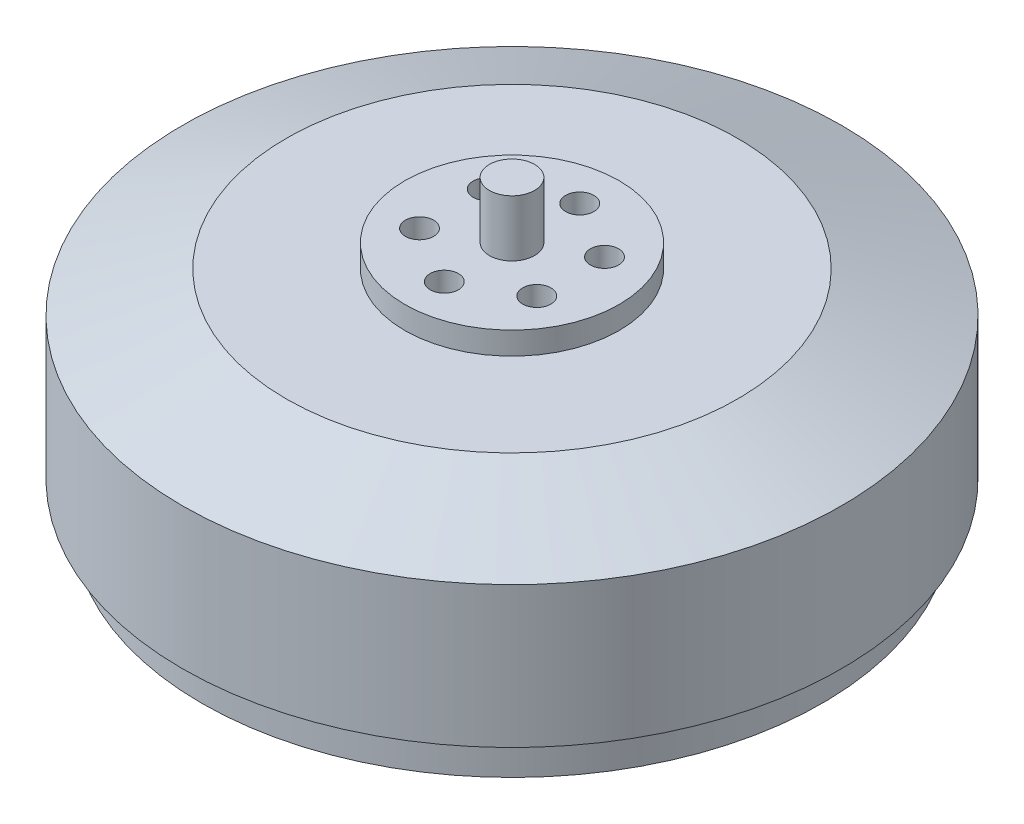
SolidWorks part; units mm, degrees
note: '?' marks a value the reader was unsure of.
ref_plane "Спереди" through (0, 0, 0) normal (0, 0, 1) x (1, 0, 0)
ref_plane "Сверху" through (0, 0, 0) normal (0, 1, 0) x (1, 0, 0)
ref_plane "Справа" through (0, 0, 0) normal (1, 0, 0) x (0, 0, -1)
ref_axis "Axis1" through (0, 5.1843, 0) along (0, 1, 0)?
sketch "Sketch1" plane through (0, 0, 0) normal (0, 0, 1) x (1, 0, 0)
  line L0 (0, 0) -> (0, -21846.0163) construction
  line L1 (0, 15.8) -> (0, -15.8)
  line L2 (0, 15.8) -> (-2, 15.8)
  line L3 (-2, 15.8) -> (-2, 10.8)
  line L4 (-2, 10.8) -> (-9.5, 10.8)
  line L5 (-9.5, 10.8) -> (-9.5, 8.8)
  line L6 (-9.5, 8.8) -> (-20, 8.8)
  line L7 (-20, 8.8) -> (-29.2, 5.2)
  line L8 (-29.2, 5.2) -> (-29.2, -7.3)
  line L9 (-29.2, -7.3) -> (-27.5, -7.3)
  line L10 (-27.5, -7.3) -> (-27.5, -10.8)
  line L11 (-27.5, -10.8) -> (-12.5, -10.8)
  line L12 (-12.5, -10.8) -> (-12.5, -15.8)
  line L13 (-12.5, -15.8) -> (0, -15.8)
  point P5 (0, 0)
  dimension "D1" = 58.4
  dimension "D2" = 4
  dimension "D3" = 19
  dimension "D4" = 40
  dimension "D5" = 5
  dimension "D6" = 2
  dimension "D7" = 3.6
  dimension "D8" = 12.5
  dimension "D9" = 3.5
  dimension "D10" = 5
  dimension "D11" = 55
  dimension "D12" = 25
revolve "Revolve1" add sketch "Sketch1" angle 360 about L0
sketch "Sketch2" plane through (0, -15.8, 0) normal (0, -1, 0) x (1, 0, 0)
  circle A0 centre (0, 12.5) radius 5
  circle A1 centre (0, 0) radius 12.5 construction
  circle A2 centre (12.5, 0) radius 5
  circle A3 centre (0, -12.5) radius 5
  circle A4 centre (-12.5, 0) radius 5
  point P14 (0, 0)
  dimension "D1" = 10
  dimension "D2" = 4
extrude "Boss-Extrude1" add sketch "Sketch2" against normal up to next
fillet "Fillet1" radius 2 8 edges at (11.5, -13.3, -4.899) (11.5, -13.3, 4.899) (-4.899, -13.3, -11.5) (4.899, -13.3, -11.5) (-11.5, -13.3, 4.899) (-11.5, -13.3, -4.899) (4.899, -13.3, 11.5) (-4.899, -13.3, 11.5)
hole_wizard "M3x0.5 Tapped Hole1" positions "Sketch3" profile "Sketch4" tap size "M3x0.5" standard "ANSI Metric"
sketch "Sketch3" plane through (0, -15.8, 0) normal (0, -1, 0) x (-1, 0, 0)
  point P0 (0, -12.5)
  point P3 (-12.5, 0)
  point P6 (0, 12.5)
  point P9 (12.5, 0)
sketch "Sketch4" plane through (0, -15.8, 12.5) normal (1, 0, 0) x (0, 0, -1)
  line L0 (0, 0) -> (0, 4.7511)
  line L1 (0, 4.7511) -> (1.25, 4)
  line L2 (1.25, 4) -> (1.25, 0)
  line L5 (1.25, 0) -> (0, 0)
  line L10 (0, 4.7511) -> (-1.25, 4) construction
  line L11 (0, -6.35) -> (0, 107.95) construction
  dimension "Tap Drill Dia." = 2.5
  dimension "Tap Drill Depth" = 4
  dimension "Drill Angle" = 118
cosmetic thread "Hole Thread1" parameters "D1"=4, "D2"=3
cosmetic thread "Hole Thread2" parameters "D1"=4, "D2"=3
cosmetic thread "Hole Thread3" parameters "D1"=4, "D2"=3
cosmetic thread "Hole Thread4" parameters "D1"=4, "D2"=3
sketch "Sketch5" plane through (0, 0, 0) normal (0, 0, 1) x (1, 0, 0)
  line L0 (0, 0) -> (0, -50000) construction
  line L1 (-4.998, -15.8) -> (4.998, -15.8) construction
  line L2 (0, -15.8) -> (-3.4, -15.8)
  line L3 (0, -15.8) -> (0, -19.3)
  line L4 (0, -19.3) -> (-3.4, -19.3)
  line L6 (-3.4, -15.8) -> (-3.4, -17.3)
  line L7 (-3.4, -17.3) -> (-5.25, -17.3)
  line L8 (-5.25, -17.3) -> (-5.25, -18.3)
  line L9 (-5.25, -18.3) -> (-3.4, -18.3)
  line L10 (-3.4, -18.3) -> (-3.4, -19.3)
  point P15 (-4.325, -18.3)
  dimension "D1" = 3.5
  dimension "D2" = 10.5
  dimension "D3" = 1
  dimension "D4" = 1
  dimension "D5" = 6.8
revolve "Revolve2" add sketch "Sketch5" angle 360 about L0
hole_wizard "M3x0.5 Tapped Hole2" positions "Sketch6" profile "Sketch7" tap size "M3x0.5" standard "ANSI Metric"
sketch "Sketch6" plane through (0, 10.8, 0) normal (0, 1, 0) x (1, 0, 0)
  point P0 (0, 6)
  point P10 (5.1962, 3)
  point P11 (5.1962, -3)
  point P12 (0, -6)
  point P13 (-5.1962, -3)
  point P14 (-5.1962, 3)
  point P15 (0, 0)
  dimension "D1" = 6
  dimension "D2" = 6
sketch "Sketch7" plane through (0, 10.8, -6) normal (1, 0, 0) x (0, 0, 1)
  line L0 (0, 0) -> (0, 4.7511)
  line L1 (0, 4.7511) -> (1.25, 4)
  line L2 (1.25, 4) -> (1.25, 0)
  line L5 (1.25, 0) -> (0, 0)
  line L10 (0, 4.7511) -> (-1.25, 4) construction
  line L11 (0, -6.35) -> (0, 107.95) construction
  dimension "Tap Drill Dia." = 2.5
  dimension "Tap Drill Depth" = 4
  dimension "Drill Angle" = 118
cosmetic thread "Hole Thread5" parameters "D1"=4, "D2"=3
cosmetic thread "Hole Thread6" parameters "D1"=4, "D2"=3
cosmetic thread "Hole Thread7" parameters "D1"=4, "D2"=3
cosmetic thread "Hole Thread8" parameters "D1"=4, "D2"=3
cosmetic thread "Hole Thread9" parameters "D1"=4, "D2"=3
cosmetic thread "Hole Thread10" parameters "D1"=4, "D2"=3
